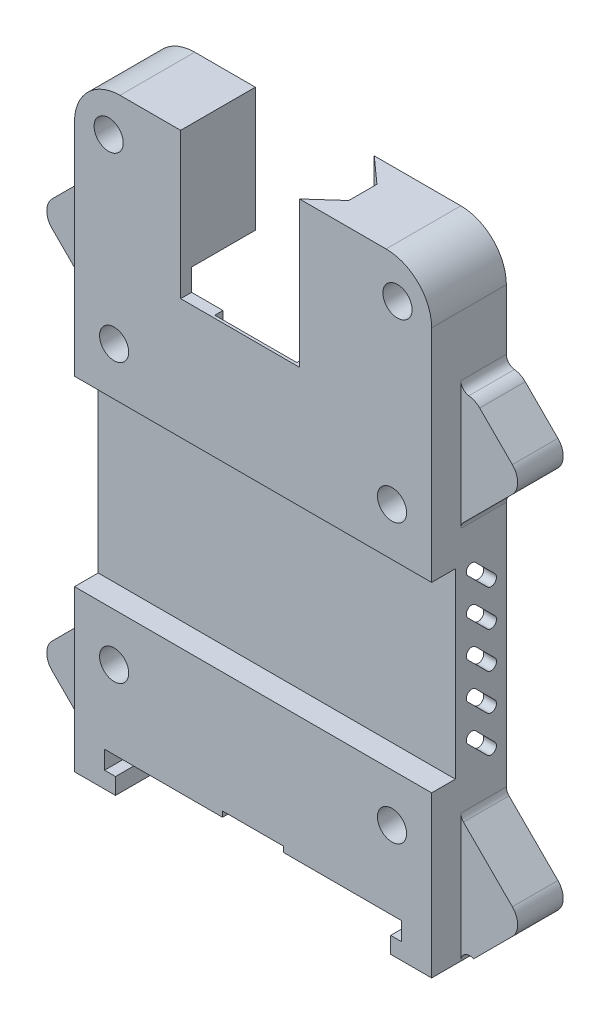
SolidWorks part; units mm, degrees
ref_plane "Front Plane" through (0, 0, 0) normal (0, 0, 1) x (1, 0, 0)
ref_plane "Top Plane" through (0, 0, 0) normal (0, 1, 0) x (1, 0, 0)
ref_plane "Right Plane" through (0, 0, 0) normal (1, 0, 0) x (0, 0, -1)
sketch "Sketch3" plane through (0, 0, 0) normal (0, 0, 1) x (1, 0, 0)
  line L0 (-18, 23) -> (18, 23)
  line L1 (-18, -23) -> (18, -23)
  line L2 (-18, -23) -> (-18, 23)
  line L3 (-19.6, 39.2) -> (19.6, 39.2)
  line L4 (18, -23) -> (18, 23)
  line L5 (-19.6, 0) -> (19.6, 0) construction
  line L6 (-7.85, 39.2) -> (-7.85, 23)
  line L7 (15.25, -15.25) -> (-15.25, -15.25) construction
  line L8 (4.95, 39.2) -> (4.95, 23)
  line L9 (0, 39.2) -> (0, -24.6) construction
  line L10 (19.6, -24.6) -> (19.6, 39.2)
  line L11 (-19.6, -24.6) -> (19.6, -24.6)
  line L12 (-19.6, -24.6) -> (-19.6, 39.2)
  line L13 (15.25, -15.25) -> (15.25, 15.25) construction
  line L14 (15.25, 15.25) -> (-15.25, 15.25) construction
  line L15 (-15.25, -15.25) -> (-15.25, 15.25) construction
  line L16 (15.25, -15.25) -> (-15.25, 15.25) construction
  line L17 (15.25, 15.25) -> (-15.25, -15.25) construction
  line L18 (-18, -23) -> (-18, 39.2) construction
  line L19 (18, -23) -> (18, 39.2) construction
  line L20 (-18.2, 23.2) -> (18.2, 23.2)
  line L21 (18.2, -23.2) -> (18.2, 23.2)
  line L22 (-18.2, -23.2) -> (18.2, -23.2)
  line L23 (-18.2, -23.2) -> (-18.2, 23.2)
  line L24 (-15.25, 18.2) -> (-18.2, 18.2)
  line L25 (-15.25, 12.3) -> (-18.2, 12.3)
  line L26 (15.25, 12.3) -> (18.2, 12.3)
  line L27 (15.25, 18.2) -> (18.2, 18.2)
  line L28 (15.25, -12.3) -> (18.2, -12.3)
  line L29 (15.25, -18.2) -> (18.2, -18.2)
  line L30 (-15.25, -12.3) -> (-18.2, -12.3)
  line L31 (-15.25, -18.2) -> (-18.2, -18.2)
  circle A4 centre (-15.25, 15.25) radius 2.95
  circle A5 centre (15.25, 15.25) radius 2.95
  circle A6 centre (15.25, -15.25) radius 2.95
  circle A7 centre (-15.25, -15.25) radius 2.95
  point P21 (0, 0)
  dimension "D3" = 36
  dimension "D4" = 46
  dimension "D5" = 39.2
  dimension "D6" = 0.2
  dimension "D1" = 1.6
extrude "Base body" add sketch "Sketch3" along normal up to surface (8.2 mm away)
sketch "Sketch5" plane through (0, 0, 0) normal (0, 0, -1) x (-1, 0, 0)
  line L1 (-18.2, 23.2) -> (18.2, 23.2)
  line L2 (-18.2, 23.2) -> (-18.2, -23.2)
  line L3 (-18.2, -23.2) -> (18.2, -23.2)
  line L4 (18.2, 23.2) -> (18.2, -23.2)
extrude "PCB cut" cut sketch "Sketch5" against normal up to surface (1.95 mm away)
sketch "Sketch7" plane through (-18.2, 0, 0) normal (1, 0, 0) x (0, 0, -1)
  line L0 (-8.2, 23.2) -> (0, 23.2) construction
  line L1 (-8.2, -23.2) -> (-7, -23.2)
  line L2 (-8.2, -23.2) -> (-8.2, 23.2)
  line L3 (-8.2, 23.2) -> (-7, 23.2)
  line L4 (-7, -23.2) -> (-7, 23.2)
  line L5 (-4.6, 0) -> (-8.2, 0) construction
  line L6 (-8.2, -11) -> (-4.6, -11)
  line L7 (-8.2, -11) -> (-8.2, 11)
  line L8 (-8.2, 11) -> (-4.6, 11)
  line L9 (-4.6, -11) -> (-4.6, 11)
  line L10 (-7, 0) -> (-8.2, 0) construction
  dimension "D1" = 22
  dimension "D2" = 1.2
  dimension "D3" = 3.6
extrude "Bottom" add sketch "Sketch7" along normal up to surface (36.4 mm away) contours L4 L3 L2 L1 | L6 L9 L8 L7 up to face at (18.2, 0, 4.75)
sketch "Sketch25" plane through (0, 0, 7) normal (0, 0, -1) x (-1, 0, 0)
  line L0 (19.6, 0) -> (-19.6, 0) construction
  line L1 (0, 39.2) -> (0, -24.6) construction
  line L2 (19.6, 0) -> (-19.6, 0)
  line L3 (0, 39.2) -> (0, -24.6)
  circle A0 centre (-15.25, 15.25) radius 1.6
  circle A2 centre (15.25, 15.25) radius 1.6
  circle A3 centre (15.25, -15.25) radius 1.6
  circle A4 centre (-15.25, -15.25) radius 1.6
  circle A5 centre (-15.85, 34.85) radius 1.6
  circle A6 centre (15.85, 34.85) radius 1.6
  circle A10 centre (-15.25, 15.25) radius 1.6 construction
  circle A11 centre (-15.85, 34.85) radius 1.6 construction
  circle A12 centre (15.85, 34.85) radius 1.6 construction
extrude "Hole cut" cut sketch "Sketch25" against normal up to next and the other way up to next contours A0 | A2 | A4 | A3 | A6 | A5
sketch "Sketch9" plane through (-18.2, 0, 0) normal (1, 0, 0) x (0, 0, -1)
  line L11 (-8.2, 10) -> (-8.2, -10)
  line L14 (-8.2, 10) -> (-5.6, 10)
  line L15 (-5.6, 10) -> (-5.6, -10)
  line L16 (-5.6, -10) -> (-8.2, -10)
  line L17 (-8.2, 10) -> (-5.6, 10)
  line L18 (-5.6, 10) -> (-5.6, -10)
  line L19 (-5.6, -10) -> (-8.2, -10)
  dimension "D1" = 1
extrude "Battery strap cut" cut sketch "Sketch9" along normal up to next and the other way up to next
sketch "Sketch11" plane through (0, -24.6, 0) normal (0, -1, 0) x (1, 0, 0)
  line L0 (-19.6, 0) -> (19.6, 0) construction
  line L1 (15.1, 0) -> (15.1, 8.2)
  line L2 (19.6, 8.2) -> (19.6, 0) construction
  line L3 (-19.6, 8.2) -> (-19.6, 0)
  line L4 (-19.6, 8.2) -> (-15.1, 8.2)
  line L6 (0, 8.2) -> (0, 0) construction
  line L7 (19.6, 8.2) -> (-19.6, 8.2) construction
  line L8 (-15.1, 0) -> (-15.1, 8.2)
  line L9 (19.6, 0) -> (15.1, 0)
  line L10 (19.6, 8.2) -> (19.6, 0)
  line L11 (19.6, 8.2) -> (15.1, 8.2)
  line L12 (-19.6, 0) -> (-15.1, 0)
  dimension "D1" = 4.5
extrude "Led strip holder" add sketch "Sketch11" along normal blind 3
sketch "Sketch14" plane through (0, 0, 8.2) normal (0, 0, 1) x (1, 0, 0)
  line L0 (-16.3, -23.8) -> (16.3, -23.8)
  line L1 (-16.1, -24) -> (16.1, -24)
  line L2 (-16.1, -24) -> (-16.1, -25.6)
  line L3 (-16.1, -25.6) -> (16.1, -25.6)
  line L4 (16.1, -24) -> (16.1, -25.6)
  line L5 (16.3, -23.8) -> (16.3, -25.8)
  line L6 (-16.3, -25.8) -> (16.3, -25.8)
  line L7 (-16.3, -23.8) -> (-16.3, -25.8)
  dimension "D1" = 0.2
extrude "Led strip cut" cut sketch "Sketch14" against normal up to next contours L5 L6 L7 L0
sketch "Sketch15" plane through (0, -23.8, 0) normal (0, -1, 0) x (1, 0, 0)
  line L0 (0, 8.2) -> (0, 0) construction
  line L1 (0, 8.2) -> (0, 0) construction
  circle A0 centre (-8, 1.35) radius 1
  circle A1 centre (-8, 1.35) radius 1 construction
  circle A2 centre (-8, 1.35) radius 0.8
  circle A3 centre (8, 1.35) radius 0.8
  dimension "D1" = 0.2
extrude "Led strip hole holder" add sketch "Sketch15" along normal blind 0.7 contours A2 | A3
sketch "Sketch20" plane through (0, -23.2, 0) normal (0, 1, 0) x (1, 0, 0)
  line L0 (0, -7) -> (0, 0) construction
  line L1 (18.2, -7) -> (-18.2, -7) construction
  line L2 (-18.2, 0) -> (18.2, 0) construction
  line L3 (4, -4.7) -> (-4, -4.7) construction
  line L4 (4, -6.2998) -> (-4, -6.2998)
  line L5 (4, -3.1002) -> (-4, -3.1002)
  arc A0 (4, -6.2998) -> (4, -3.1002) centre (4, -4.7) ccw
  arc A1 (-4, -3.1002) -> (-4, -6.2998) centre (-4, -4.7) ccw
  point P8 (0, -4.7)
  dimension "D3" = 1.5998
  dimension "D1" = 8
  dimension "D2" = 4.7
extrude "Led strip wire hole" cut sketch "Sketch20" against normal up to next
sketch "Sketch16" plane through (0, 39.2, 0) normal (0, 1, 0) x (1, 0, 0)
  line L0 (-7.95, 0) -> (5.0998, 0)
  line L1 (4.95, 0) -> (7.85, -2.6)
  line L2 (-7.95, -8.2) -> (-7.95, 0)
  line L3 (-7.95, -8.2) -> (-7.95, 0)
  line L4 (7.85, -2.6) -> (7.85, -5.6)
  line L5 (7.85, -5.6) -> (4.95, -8.2)
  line L6 (5.0998, -8.2) -> (-7.95, -8.2)
  line L7 (5.0998, 0) -> (7.95, -2.5553)
  line L8 (7.95, -2.5553) -> (7.95, -5.6447)
  line L9 (7.95, -5.6447) -> (5.0998, -8.2)
  line L10 (5.0168, 0.0745) -> (7.95, -2.5553) construction
  line L11 (7.95, -5.6447) -> (5.0168, -8.2745) construction
  line L12 (4.95, 0) -> (19.6, 0) construction
  line L14 (19.6, -8.2) -> (4.95, -8.2) construction
  dimension "D1" = 0.1
  dimension "D2" = 0.1
extrude "XT60 cut" cut sketch "Sketch16" against normal up to surface (16 mm away) contours L7 L8 L9 L6 L3 L0 up to face at (-13.025, 23.2, 3.5)
sketch "Sketch21" plane through (0, 0, 0) normal (0, 0, -1) x (-1, 0, 0)
  line L0 (18.2, 23.2) -> (-18.2, 23.2) construction
  line L1 (9.35, 23.2) -> (18.2, 23.2)
  line L2 (9.35, 23.2) -> (9.35, 32.2)
  line L3 (9.35, 32.2) -> (18.2, 32.2)
  line L4 (18.2, 23.2) -> (18.2, 32.2)
  line L5 (0, 39.2) -> (0, -24.6) construction
  line L6 (0, 39.2) -> (0, -24.6) construction
  line L7 (-18.2, 23.2) -> (-18.2, 32.2)
  line L8 (-9.35, 32.2) -> (-18.2, 32.2)
  line L9 (-9.35, 23.2) -> (-9.35, 32.2)
  line L10 (-9.35, 23.2) -> (-18.2, 23.2)
  line L11 (18.2, 32.2) -> (19.6, 32.2) construction
  line L13 (19.6, -24.6) -> (19.6, 39.2) construction
  line L14 (9.35, 32.2) -> (7.95, 32.2) construction
  line L15 (7.95, 23.2) -> (7.95, 39.2) construction
  line L16 (18.2, -23.2) -> (18.2, 23.2) construction
  dimension "D2" = 9
extrude "Wire pocket" cut sketch "Sketch21" against normal up to surface (7 mm away) up to face at (-0.108, 16.9143, 7)
sketch "Sketch22" plane through (0, 0, 0) normal (0, 0, 1) x (1, 0, 0)
  line L0 (0, 39.2) -> (0, -23.8) construction
  line L1 (-7.85, 39.2) -> (4.95, 39.2) construction
  line L2 (-16.3, -23.8) -> (16.3, -23.8) construction
  line L3 (-19.6, 0) -> (19.6, 0) construction
  line L4 (-19.6, -10) -> (-19.6, 10) construction
  line L5 (19.6, 10) -> (19.6, -10) construction
  line L6 (-19.6, 13.9431) -> (-26.6711, 21.0142)
  line L7 (-19.6, 39.2) -> (-19.6, 10) construction
  line L8 (-26.6711, 21.0142) -> (-21.0142, 26.6711)
  line L9 (-21.0142, 26.6711) -> (-19.6, 25.2569)
  line L10 (-19.6, 25.2569) -> (-19.6, 13.9431)
  line L14 (-23.8426, 23.8426) -> (-19.6, 19.6) construction
  dimension "D1" = 45
  dimension "D2" = 10
  dimension "D3" = 8
extrude "ESC wire extrude" add sketch "Sketch22" along normal blind 5
sketch "Sketch23" plane through (0, 0, 0) normal (0, 0, -1) x (-1, 0, 0)
  line L0 (18.2, 24.4083) -> (18.2, 18.2)
  line L6 (20.4485, 24.4083) -> (18.2, 24.4083)
  line L7 (18.2, -23.2) -> (18.2, 32.2) construction
  line L8 (18.2, 18.2) -> (22.1598, 18.2)
  line L9 (20.4485, 24.4083) -> (21.0142, 24.974)
  line L10 (24.974, 21.0142) -> (18.7515, 14.7917)
  line L11 (21.0142, 24.974) -> (24.974, 21.0142)
  line L12 (20.4485, 24.4083) -> (21.0142, 24.974)
  line L13 (24.974, 21.0142) -> (22.1598, 18.2)
  line L14 (21.0142, 24.974) -> (24.974, 21.0142)
  dimension "D1" = 1.2
extrude "ESC wire pocket" cut sketch "Sketch23" against normal offset from surface (3.8 mm away) 1.2 up to face at (-21.7213, 21.7213, 5)
mirror "Mirror left-right" about plane through (0, 0, 0) normal (1, 0, 0) of "ESC wire extrude", "ESC wire pocket"
mirror "Mirror top-bottom" about plane through (0, 0, 0) normal (0, 1, 0) of "Mirror left-right", "ESC wire extrude", "ESC wire pocket"
fillet "Inner fillet" radius 2 6 edges at (-18.2, 21.3042, 3.8) (-18.2, 24.4083, 1.9) (18.2, 24.4083, 1.9) (18.2, 21.3042, 3.8) (18.2, -20.7, 3.8) (-18.2, -20.7, 3.8)
fillet "Outer fillet" radius 1 8 edges at (-19.6, 25.2569, 2.5) (-19.6, 13.9431, 2.5) (19.6, 13.9431, 2.5) (19.6, -13.9431, 2.5) (-19.6, -13.9431, 2.5) (19.6, -25.2569, 2.5) (-19.6, -25.2569, 2.5) (19.6, 25.2569, 2.5)
fillet "Fillet2" radius 2 6 edges at (-21.0142, 26.6711, 2.5) (-26.6711, 21.0142, 2.5) (-26.6711, -21.0142, 2.5) (26.6711, -21.0142, 2.5) (21.0142, 26.6711, 2.5) (26.6711, 21.0142, 2.5)
sketch "Sketch24" plane through (-19.6, 0, 0) normal (-1, 0, 0) x (0, 0, 1)
  line L0 (4.1, 39.2) -> (4.1, -9.4816) construction
  line L1 (8.2, 39.2) -> (0, 39.2) construction
  line L3 (3.8, 9.0607) -> (1.6787, 6.9393) construction
  line L4 (4.221, 8.6397) -> (2.0997, 6.5184)
  line L5 (3.379, 9.4816) -> (1.2577, 7.3603)
  line L6 (3.8, 5.0607) -> (1.6787, 2.9393) construction
  line L7 (4.221, 4.6397) -> (2.0997, 2.5184)
  line L8 (3.379, 5.4816) -> (1.2577, 3.3603)
  line L9 (3.8, 1.0607) -> (1.6787, -1.0607) construction
  line L10 (4.221, 0.6397) -> (2.0997, -1.4816)
  line L11 (3.379, 1.4816) -> (1.2577, -0.6397)
  line L12 (3.8, -2.9393) -> (1.6787, -5.0607) construction
  line L13 (4.221, -3.3603) -> (2.0997, -5.4816)
  line L14 (3.379, -2.5184) -> (1.2577, -4.6397)
  line L15 (3.8, -6.9393) -> (1.6787, -9.0607) construction
  line L16 (4.221, -7.3603) -> (2.0997, -9.4816)
  line L17 (3.379, -6.5184) -> (1.2577, -8.6397)
  line L18 (5.6, 0) -> (0, 0) construction
  line L19 (5.6, -10) -> (5.6, 10) construction
  line L20 (0, -13.5289) -> (0, 13.5289) construction
  line L21 (3.8, -6.9393) -> (3.8, 9.0607) construction
  arc A0 (4.221, 8.6397) -> (3.379, 9.4816) centre (3.8, 9.0607) ccw
  arc A1 (1.2577, 7.3603) -> (2.0997, 6.5184) centre (1.6787, 6.9393) ccw
  arc A2 (4.221, 4.6397) -> (3.379, 5.4816) centre (3.8, 5.0607) ccw
  arc A3 (1.2577, 3.3603) -> (2.0997, 2.5184) centre (1.6787, 2.9393) ccw
  arc A4 (4.221, 0.6397) -> (3.379, 1.4816) centre (3.8, 1.0607) ccw
  arc A5 (1.2577, -0.6397) -> (2.0997, -1.4816) centre (1.6787, -1.0607) ccw
  arc A6 (4.221, -3.3603) -> (3.379, -2.5184) centre (3.8, -2.9393) ccw
  arc A7 (1.2577, -4.6397) -> (2.0997, -5.4816) centre (1.6787, -5.0607) ccw
  arc A8 (4.221, -7.3603) -> (3.379, -6.5184) centre (3.8, -6.9393) ccw
  arc A9 (1.2577, -8.6397) -> (2.0997, -9.4816) centre (1.6787, -9.0607) ccw
  point P4 (4.221, -9.4816)
  point P8 (2.7393, 8)
  point P17 (2.7393, 4)
  point P24 (2.7393, 0)
  point P31 (2.7393, -4)
  point P38 (2.7393, -8)
  dimension "D1" = 0.5954
  dimension "D2" = 45
  dimension "D3" = 3
  dimension "D5" = 4
  dimension "D6" = 0.3
  dimension "D4" = 5
extrude "Ventilation cut" cut sketch "Sketch24" against normal through all both and the other way through all
fillet "Fillet1" radius 5 2 edges at (19.6, 39.2, 4.1) (-19.6, 39.2, 4.1)
sketch "Sketch26" plane through (0, 0, 0) normal (0, 0, -1) x (-1, 0, 0)
  line L0 (-9.35, 23.2) -> (-9.35, 32.2) construction
  line L1 (-9.35, 25.6) -> (9.35, 25.6)
  line L2 (-9.35, 25.6) -> (-9.35, 23.2)
  line L3 (-9.35, 23.2) -> (9.35, 23.2)
  line L4 (9.35, 25.6) -> (9.35, 23.2)
  line L5 (-9.35, 25.6) -> (9.35, 23.2) construction
  line L6 (-9.35, 23.2) -> (9.35, 25.6) construction
  point P4 (0, 24.4)
  dimension "D1" = 2.4
extrude "Capacitor cut" cut sketch "Sketch26" against normal up to surface (7 mm away) up to face at (-0.084, 20.3111, 7)
sketch "Sketch27" plane through (0, 0, 7) normal (0, 0, -1) x (-1, 0, 0)
  line L0 (-6.4383, 23.2) -> (7.95, 23.2) construction
  line L1 (-4.5, 23.2) -> (4.5, 23.2)
  line L2 (-4.5, 23.2) -> (-4.5, 11.6)
  line L3 (-4.5, 11.6) -> (4.5, 11.6)
  line L4 (4.5, 23.2) -> (4.5, 11.6)
  line L5 (-4.5, 23.2) -> (4.5, 11.6) construction
  line L6 (-4.5, 11.6) -> (4.5, 23.2) construction
  line L7 (-9.35, 25.6) -> (9.35, 25.6) construction
  line L9 (0, 25.6) -> (0, 11.6) construction
  point P4 (0, 17.4)
  dimension "D1" = 11.6
  dimension "D2" = 9
extrude "Cut-Extrude2" cut sketch "Sketch27" against normal offset from surface (0.9 mm away) 0.3 up to face at (13.65, -15.25, 8.2)
sketch "Sketch28" plane through (0, 0, 8.2) normal (0, 0, 1) x (1, 0, 0)
  line L0 (-16.3, -23.8) -> (16.3, -23.8) construction
  line L1 (-3.35, -23.8) -> (3.35, -23.8)
  line L2 (-3.35, -23.8) -> (-3.35, -23.2)
  line L3 (-3.35, -23.2) -> (3.35, -23.2)
  line L4 (3.35, -23.8) -> (3.35, -23.2)
  line L5 (-3.35, -23.8) -> (3.35, -23.2) construction
  line L6 (-3.35, -23.2) -> (3.35, -23.8) construction
  line L7 (0, -10) -> (0, -23.8) construction
  line L8 (-19.6, -10) -> (19.6, -10) construction
  line L9 (18.2, -23.2) -> (-18.2, -23.2) construction
  point P4 (0, -23.5)
  dimension "D1" = 6.7
extrude "Cut-Extrude3" cut sketch "Sketch28" against normal up to next
